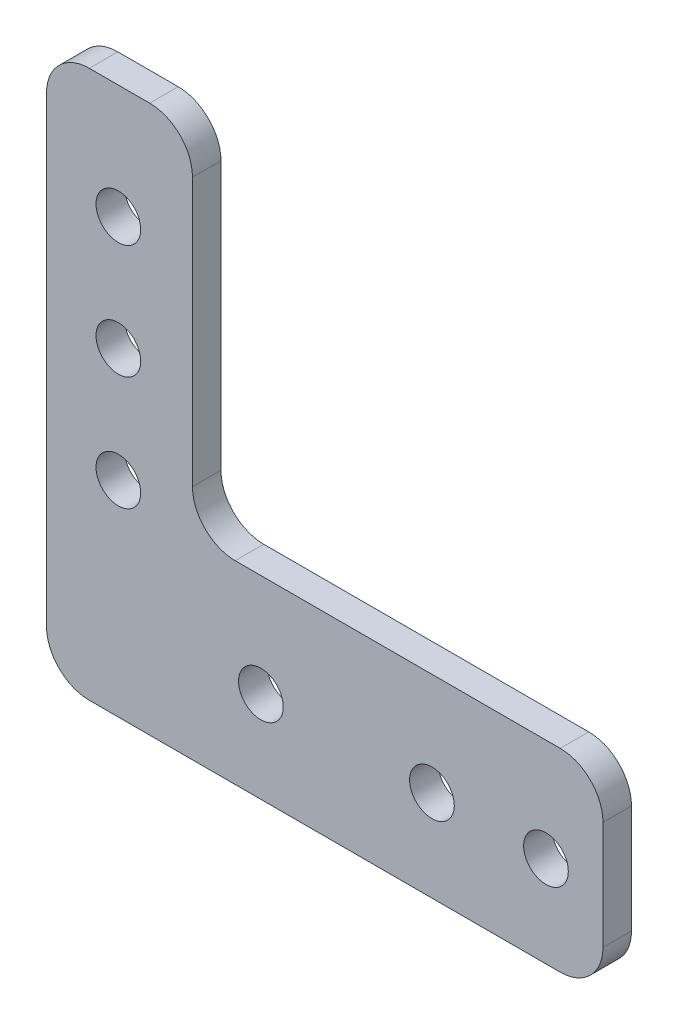
SolidWorks part; units mm, degrees
material "6061-T6 (SS)"
ref_plane "Front Plane" through (0, 0, 0) normal (0, 0, 1) x (1, 0, 0)
ref_plane "Top Plane" through (0, 0, 0) normal (0, 1, 0) x (1, 0, 0)
ref_plane "Right Plane" through (0, 0, 0) normal (1, 0, 0) x (0, 0, -1)
sketch "Sketch1" plane through (0, 0, 0) normal (0, 0, 1) x (1, 0, 0)
  line L1 (-34.925, -31.75) -> (34.925, -31.75)
  line L2 (-34.925, -31.75) -> (-34.925, 31.75)
  line L3 (-34.925, 31.75) -> (34.925, 31.75)
  line L4 (34.925, -31.75) -> (34.925, 31.75)
  line L5 (-34.925, -31.75) -> (34.925, 31.75) construction
  line L6 (-34.925, 31.75) -> (34.925, -31.75) construction
  line L7 (34.925, 31.75) -> (-10.795, 31.75)
  line L8 (34.925, 31.75) -> (34.925, -7.62)
  line L9 (34.925, -7.62) -> (-10.795, -7.62)
  line L10 (-10.795, 31.75) -> (-10.795, -7.62)
  line L11 (-34.925, -31.75) -> (-27.051, -31.75)
  line L12 (-34.925, -31.75) -> (-34.925, 31.75)
  line L13 (-34.925, 31.75) -> (-27.051, 31.75)
  line L14 (-27.051, -31.75) -> (-27.051, 31.75)
  line L15 (-27.051, -31.75) -> (34.925, -31.75)
  line L16 (-27.051, -31.75) -> (-27.051, -29.21)
  line L17 (-27.051, -29.21) -> (34.925, -29.21)
  line L18 (34.925, -31.75) -> (34.925, -29.21)
  circle A0 centre (-19.05, -19.05) radius 2.4892
  circle A1 centre (-19.05, -6.35) radius 2.4892
  circle A2 centre (-19.05, 6.35) radius 2.4892
  circle A3 centre (-19.05, 19.05) radius 2.4892
  circle A4 centre (-3.175, -19.05) radius 2.4892
  circle A5 centre (15.875, -19.05) radius 2.4892
  circle A6 centre (28.575, -19.05) radius 2.4892
  point P0 (0, 0)
  dimension "D7" = 4.9784
  dimension "D14" = 15.875
  dimension "D1" = 69.85
  dimension "D2" = 63.5
  dimension "D3" = 24.13
  dimension "D4" = 24.13
  dimension "D5" = 7.874
  dimension "D6" = 63.5
  dimension "D8" = 15.875
  dimension "D9" = 12.7
  dimension "D10" = 12.7
  dimension "D11" = 12.7
  dimension "D12" = 12.7
  dimension "D13" = 12.7
  dimension "D15" = 50.8
  dimension "D16" = 2.54
extrude "Boss-Extrude1" add sketch "Sketch1" along normal blind 3.175 contours L14 L17 L4 L9 L10 L3 A6 A5 A4 A3 A2 A1 A0 | A0 region at (-3.3461, -8.582, 0) region at (-19.05, -19.05, 0)
fillet "Fillet1" radius 4.7625 6 edges at (-27.051, 31.75, 1.5875) (-10.795, 31.75, 1.5875) (-10.795, -7.62, 1.5875) (34.925, -7.62, 1.5875) (34.925, -29.21, 1.5875) (-27.051, -29.21, 1.5875)
